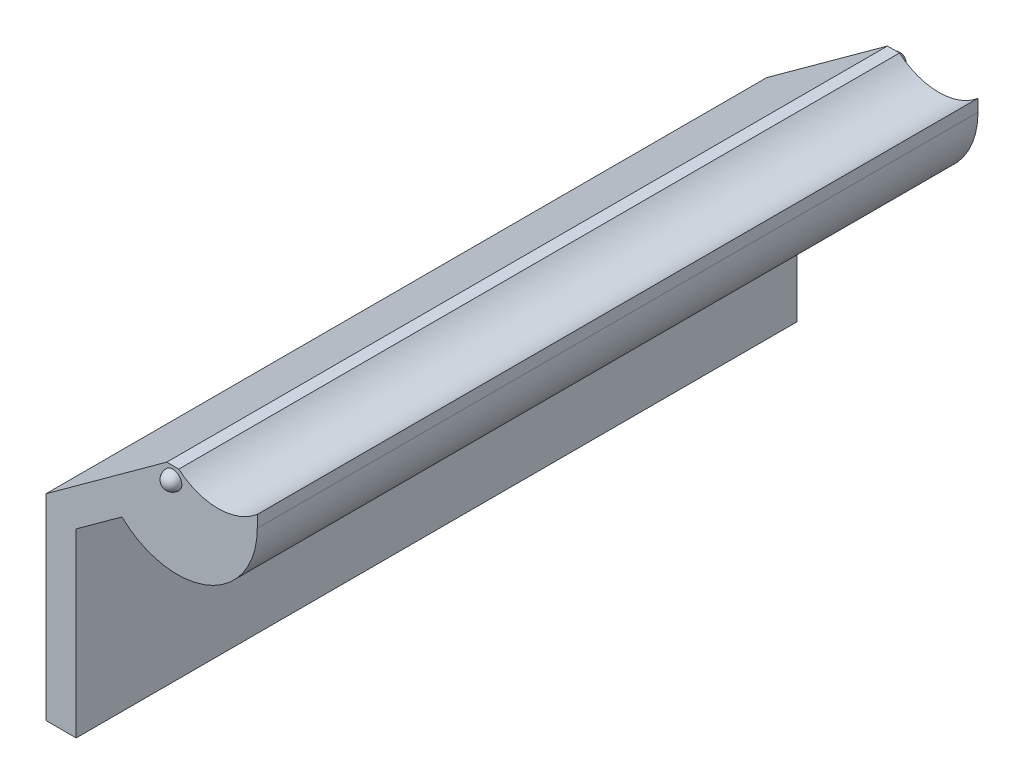
SolidWorks part; units mm, degrees
ref_plane "Front Plane" through (0, 0, 0) normal (0, 0, 1) x (1, 0, 0)
ref_plane "Top Plane" through (0, 0, 0) normal (0, 1, 0) x (1, 0, 0)
ref_plane "Right Plane" through (0, 0, 0) normal (1, 0, 0) x (0, 0, -1)
sketch "Sketch1" plane through (0, 0, 0) normal (0, 0, 1) x (1, 0, 0)
  line L0 (-19.05, -41.4676) -> (-9.4202, -34.4711)
  line L2 (-25.4, -38.2321) -> (-25.4, -79.5676)
  line L3 (-25.4, -79.5676) -> (-19.05, -79.5676)
  line L4 (-19.05, -41.4676) -> (-19.05, -79.5676)
  line L5 (-25.4, -38.2321) -> (0, -19.7779)
  line L6 (19.05, -19.7779) -> (19.05, -22.3179)
  line L7 (0, -38.9998) -> (0, -150.6026) construction
  line L9 (0, 29.1888) -> (0, -19.7779) construction
  line L11 (0, -19.7779) -> (2.54, -19.7779)
  arc A0 (-9.4202, -34.4711) -> (19.05, -22.3179) centre (2.221, -22.3179) ccw
  arc A1 (2.54, -19.7779) -> (19.05, -19.7779) centre (10.795, -10.1268) ccw
  dimension "D9" = 12.7
  dimension "D1" = 6.35
  dimension "D2" = 6.35
  dimension "D3" = 2.54
  dimension "D4" = 126
  dimension "D5" = 19.05
  dimension "D6" = 38.1
  dimension "D7" = 19.05
  dimension "D8" = 2.54
extrude "Boss-Extrude1" add sketch "Sketch1" along normal mid plane 151.638
sketch "Sketch2" plane through (0, 0, 75.819) normal (0, 0, 1) x (1, 0, 0)
  line L0 (2.54, -19.7779) -> (0, -19.7779) construction
  line L2 (1.27, -20.4129) -> (1.27, -24.2229)
  arc A0 (1.27, -24.2229) -> (1.27, -20.4129) centre (1.27, -22.3179) ccw
  point P4 (1.27, -19.7779)
  dimension "D1" = 3.81
revolve "Revolve1" add sketch "Sketch2" angle 360 about L2
sketch "Sketch3" plane through (0, 0, -75.819) normal (0, 0, -1) x (-1, 0, 0)
  line L0 (-1.27, -20.4129) -> (-1.27, -24.2229)
  arc A0 (-1.27, -24.2229) -> (-1.27, -20.4129) centre (-1.27, -22.3179) ccw
  circle A1 centre (-1.27, -22.3179) radius 1.905 construction
revolve "Revolve2" add sketch "Sketch3" angle 360 about L0
